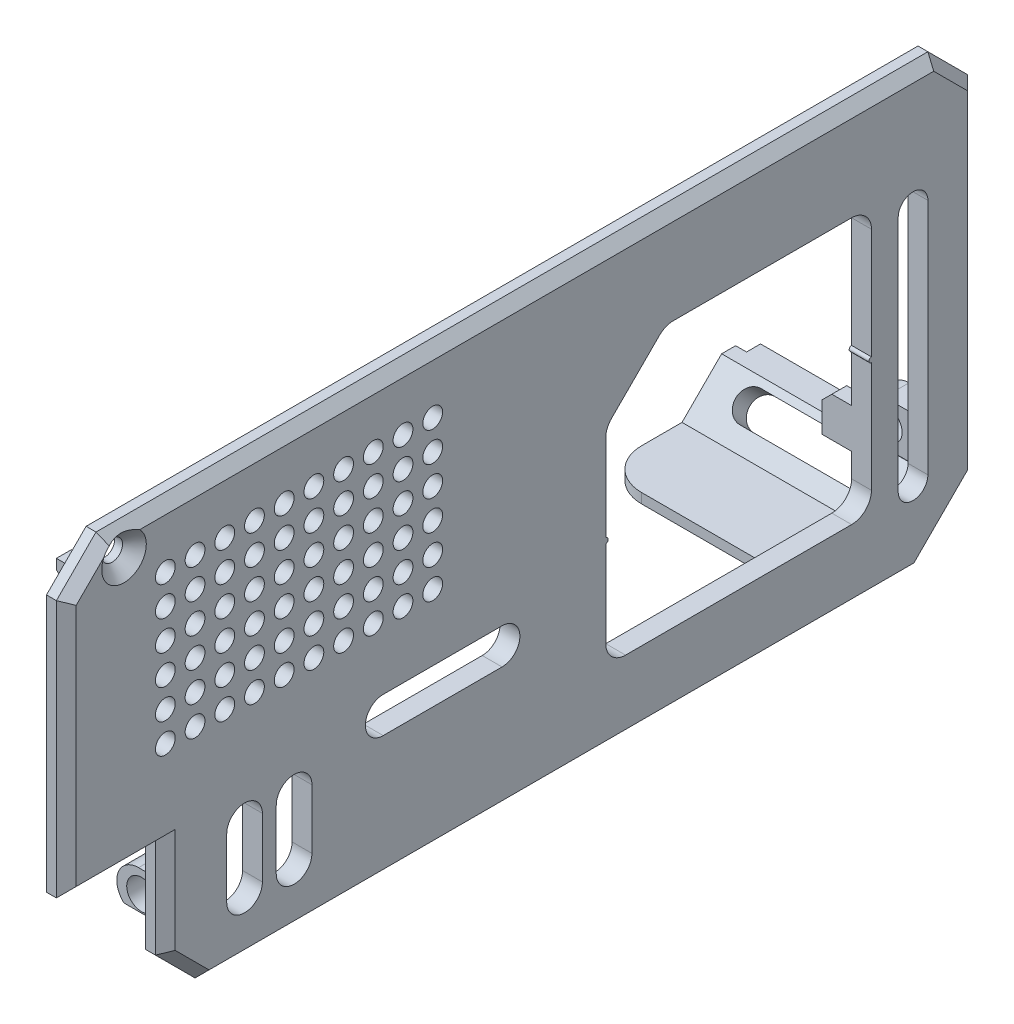
SolidWorks part; units mm, degrees
ref_plane "前视基准面" through (0, 0, 0) normal (0, 0, 1) x (1, 0, 0)
ref_plane "上视基准面" through (0, 0, 0) normal (0, 1, 0) x (1, 0, 0)
ref_plane "右视基准面" through (0, 0, 0) normal (1, 0, 0) x (0, 0, -1)
other "Configuration Table"
sketch "草图1" plane through (0, 0, 0) normal (1, 0, 0) x (0, 0, -1)
  line L0 (61.8678, 29.485) -> (61.8678, -4.515) construction
  line L5 (-16.1322, -10.515) -> (-15.718, -9.515) construction
  line L6 (-20.1322, -6.515) -> (-16.1322, -10.515) construction
  line L14 (61.8678, 29.485) -> (57.8678, 33.485)
  line L15 (61.8678, 29.485) -> (61.8678, -4.515)
  line L16 (55.8678, -10.515) -> (61.8678, -4.515)
  line L17 (-16.1322, -10.515) -> (55.8678, -10.515)
  line L18 (-20.1322, -6.515) -> (-16.1322, -10.515)
  line L19 (-20.1322, 3.485) -> (-20.1322, -6.515)
  line L20 (-30.1322, 3.485) -> (-20.1322, 3.485)
  line L21 (-30.1322, 29.485) -> (-30.1322, 3.485)
  line L22 (-26.1322, 33.485) -> (57.8678, 33.485)
  line L23 (-26.1322, 33.485) -> (-30.1322, 29.485)
extrude "凸台-拉伸1" add sketch "草图1" along normal blind 2
chamfer "倒角1" distance 1 angle 45 10 edges at (2, 31.485, -59.8678) (2, 12.485, -61.8678) (2, -7.515, -58.8678) (2, -10.515, -19.8678) (2, -8.515, 18.1322) (2, -1.515, 20.1322) (2, 3.485, 25.1322) (2, 16.485, 30.1322) (2, 31.485, 28.1322) (2, 33.485, -15.8678)
sketch "草图2" plane through (0, 0, 0) normal (-1, 0, 0) x (0, 0, 1)
  line L10 (-58.7678, 28.2009) -> (-58.7678, -3.231)
  line L11 (-58.7678, -3.231) -> (-54.5838, -7.415)
  line L12 (-54.5838, -7.415) -> (14.8481, -7.415)
  line L13 (14.8481, -7.415) -> (17.0322, -5.231)
  line L14 (17.0322, -5.231) -> (17.0322, 6.585)
  line L15 (17.0322, 6.585) -> (27.0322, 6.585)
  line L16 (27.0322, 6.585) -> (27.0322, 28.2009)
  line L17 (27.0322, 28.2009) -> (24.8481, 30.385)
  line L18 (24.8481, 30.385) -> (-56.5838, 30.385)
  line L19 (-56.5838, 30.385) -> (-58.7678, 28.2009)
  line L20 (-59.7678, 28.6151) -> (-59.7678, -3.6452)
  line L21 (-59.7678, -3.6452) -> (-54.998, -8.415)
  line L22 (-54.998, -8.415) -> (15.2623, -8.415)
  line L23 (15.2623, -8.415) -> (18.0322, -5.6452)
  line L24 (18.0322, -5.6452) -> (18.0322, 5.585)
  line L25 (18.0322, 5.585) -> (28.0322, 5.585)
  line L26 (28.0322, 5.585) -> (28.0322, 28.6151)
  line L27 (28.0322, 28.6151) -> (25.2623, 31.385)
  line L28 (25.2623, 31.385) -> (-56.998, 31.385)
  line L29 (-56.998, 31.385) -> (-59.7678, 28.6151)
  line L30 (-59.7678, 28.6151) -> (-59.7678, -3.6452)
  line L31 (-59.7678, -3.6452) -> (-54.998, -8.415)
  line L32 (-54.998, -8.415) -> (15.2623, -8.415)
  line L33 (15.2623, -8.415) -> (18.0322, -5.6452)
  line L34 (18.0322, -5.6452) -> (18.0322, 5.585)
  line L35 (18.0322, 5.585) -> (28.0322, 5.585)
  line L36 (28.0322, 5.585) -> (28.0322, 28.6151)
  line L37 (28.0322, 28.6151) -> (25.2623, 31.385)
  line L38 (25.2623, 31.385) -> (-56.998, 31.385)
  line L39 (-56.998, 31.385) -> (-59.7678, 28.6151)
  dimension "D1" = 2.1
  dimension "D2" = 1
extrude "凸台-拉伸2" add sketch "草图2" along normal blind 1
sketch "草图3" plane through (0, 0, 0) normal (-1, 0, 0) x (0, 0, 1)
  line L0 (16.1322, -10.515) -> (-55.8678, -10.515) construction
  line L1 (-52.6678, 1.385) -> (-51.1678, 1.385)
  line L2 (-52.6678, 1.385) -> (-52.6678, 5.385)
  line L3 (-52.6678, 5.385) -> (-51.1678, 5.385)
  line L4 (-51.1678, 1.385) -> (-51.1678, 5.385)
  line L5 (0.1322, 1.385) -> (1.6322, 1.385)
  line L6 (0.1322, 1.385) -> (0.1322, 5.385)
  line L7 (0.1322, 5.385) -> (1.6322, 5.385)
  line L8 (1.6322, 1.385) -> (1.6322, 5.385)
  line L9 (-61.8678, -4.515) -> (-61.8678, 29.485) construction
  dimension "D1" = 1.5
  dimension "D2" = 15.9
  dimension "D3" = 4
  dimension "D4" = 9.2
  dimension "D5" = 62
extrude "凸台-拉伸3" add sketch "草图3" along normal blind 3
chamfer "倒角2" distance 1 angle 45 2 edges at (-3, 5.385, 0.8822) (-3, 5.385, -51.9178)
sketch "草图4" plane through (-60, 0, 0) normal (-1, 0, 0) x (0, 0, 1)
  line L0 (30.1322, 29.485) -> (30.1322, 3.485) construction
  line L1 (-57.8678, 33.485) -> (26.1322, 33.485) construction
  circle A0 centre (20.1322, 27.485) radius 1
  circle A1 centre (17.1322, 27.485) radius 1
  circle A2 centre (14.1322, 27.485) radius 1
  circle A3 centre (11.1322, 27.485) radius 1
  circle A4 centre (8.1322, 27.485) radius 1
  circle A5 centre (5.1322, 27.485) radius 1
  circle A7 centre (17.1322, 24.485) radius 1
  circle A8 centre (14.1322, 24.485) radius 1
  circle A9 centre (11.1322, 24.485) radius 1
  circle A10 centre (8.1322, 24.485) radius 1
  circle A11 centre (5.1322, 24.485) radius 1
  circle A13 centre (17.1322, 21.485) radius 1
  circle A14 centre (14.1322, 21.485) radius 1
  circle A15 centre (11.1322, 21.485) radius 1
  circle A16 centre (8.1322, 21.485) radius 1
  circle A17 centre (5.1322, 21.485) radius 1
  circle A19 centre (17.1322, 18.485) radius 1
  circle A20 centre (14.1322, 18.485) radius 1
  circle A21 centre (11.1322, 18.485) radius 1
  circle A22 centre (8.1322, 18.485) radius 1
  circle A23 centre (5.1322, 18.485) radius 1
  circle A25 centre (17.1322, 15.485) radius 1
  circle A26 centre (14.1322, 15.485) radius 1
  circle A27 centre (11.1322, 15.485) radius 1
  circle A28 centre (8.1322, 15.485) radius 1
  circle A29 centre (5.1322, 15.485) radius 1
  circle A31 centre (17.1322, 12.485) radius 1
  circle A32 centre (14.1322, 12.485) radius 1
  circle A33 centre (11.1322, 12.485) radius 1
  circle A34 centre (8.1322, 12.485) radius 1
  circle A35 centre (5.1322, 12.485) radius 1
  circle A43 centre (20.1322, 24.485) radius 1
  circle A44 centre (20.1322, 21.485) radius 1
  circle A45 centre (20.1322, 18.485) radius 1
  circle A46 centre (20.1322, 15.485) radius 1
  circle A47 centre (20.1322, 12.485) radius 1
  circle A48 centre (2.1322, 27.485) radius 1
  circle A49 centre (-0.8678, 27.485) radius 1
  circle A50 centre (-3.8678, 27.485) radius 1
  circle A51 centre (-6.8678, 27.485) radius 1
  circle A52 centre (2.1322, 24.485) radius 1
  circle A53 centre (-0.8678, 24.485) radius 1
  circle A54 centre (-3.8678, 24.485) radius 1
  circle A55 centre (-6.8678, 24.485) radius 1
  circle A56 centre (2.1322, 21.485) radius 1
  circle A57 centre (-0.8678, 21.485) radius 1
  circle A58 centre (-3.8678, 21.485) radius 1
  circle A59 centre (-6.8678, 21.485) radius 1
  circle A60 centre (2.1322, 18.485) radius 1
  circle A61 centre (-0.8678, 18.485) radius 1
  circle A62 centre (-3.8678, 18.485) radius 1
  circle A63 centre (-6.8678, 18.485) radius 1
  circle A64 centre (2.1322, 15.485) radius 1
  circle A65 centre (-0.8678, 15.485) radius 1
  circle A66 centre (-3.8678, 15.485) radius 1
  circle A67 centre (-6.8678, 15.485) radius 1
  circle A68 centre (2.1322, 12.485) radius 1
  circle A69 centre (-0.8678, 12.485) radius 1
  circle A70 centre (-3.8678, 12.485) radius 1
  circle A71 centre (-6.8678, 12.485) radius 1
  dimension "D3" = 2
  dimension "D1" = 10
  dimension "D2" = 6
  dimension "D4" = 10
  dimension "D5" = 6
extrude "切除-拉伸1" cut sketch "草图4" against normal up to next
sketch "草图5" plane through (0, 0, 0) normal (-1, 0, 0) x (0, 0, 1)
  line L0 (20.1322, 3.485) -> (20.1322, -6.515) construction
  line L1 (16.1322, -10.515) -> (-55.8678, -10.515) construction
  line L4 (13.9322, -4.515) -> (13.9322, 1.485)
  line L5 (10.3322, 1.485) -> (10.3322, -4.515)
  line L8 (5.3322, 1.485) -> (5.3322, -4.515)
  line L9 (8.9322, -4.515) -> (8.9322, 1.485)
  arc A4 (13.9322, 1.485) -> (10.3322, 1.485) centre (12.1322, 1.485) ccw
  arc A5 (10.3322, -4.515) -> (13.9322, -4.515) centre (12.1322, -4.515) ccw
  arc A8 (8.9322, 1.485) -> (5.3322, 1.485) centre (7.1322, 1.485) ccw
  arc A9 (5.3322, -4.515) -> (8.9322, -4.515) centre (7.1322, -4.515) ccw
  dimension "D1" = 8
  dimension "D2" = 5
  dimension "D3" = 6
extrude "切除-拉伸2" cut sketch "草图5" against normal up to next
sketch "草图6" plane through (0, 0, 0) normal (-1, 0, 0) x (0, 0, 1)
  line L0 (-55.3678, 21.485) -> (-55.3678, -2.515) construction
  line L1 (-53.8678, 21.485) -> (-53.8678, -2.515)
  line L2 (-56.8678, 21.485) -> (-56.8678, -2.515)
  line L3 (-57.8678, 33.485) -> (26.1322, 33.485) construction
  line L4 (16.1322, -10.515) -> (-55.8678, -10.515) construction
  line L5 (-61.8678, -4.515) -> (-61.8678, 29.485) construction
  arc A0 (-53.8678, 21.485) -> (-56.8678, 21.485) centre (-55.3678, 21.485) ccw
  arc A1 (-56.8678, -2.515) -> (-53.8678, -2.515) centre (-55.3678, -2.515) ccw
  point P2 (-55.3678, 9.485)
  dimension "D4" = 1.5
  dimension "D1" = 12
  dimension "D2" = 8
  dimension "D3" = 6.5
extrude "切除-拉伸3" cut sketch "草图6" against normal up to next
sketch "草图7" plane through (0, 0, 0) normal (-1, 0, 0) x (0, 0, 1)
  line L1 (22.6322, 27.185) -> (24.1322, 27.185)
  line L2 (22.6322, 27.185) -> (22.6322, 25.185)
  line L3 (22.6322, 25.185) -> (24.1322, 25.185)
  line L4 (24.1322, 27.185) -> (24.1322, 25.185)
  line L8 (22.6322, 23.235) -> (22.6322, 27.235) construction
  line L9 (29.3879, 25.185) -> (12.7179, 25.185) construction
  dimension "D1" = 1.5
  dimension "D2" = 2
extrude "凸台-拉伸4" add sketch "草图7" along normal blind 5
chamfer "倒角3" distance 1 angle 45 1 edges at (-5, 25.185, 23.3822)
sketch "草图9" plane through (0, 0, 0) normal (-1, 0, 0) x (0, 0, 1)
  line L0 (16.1322, -10.515) -> (-55.8678, -10.515) construction
  line L2 (-51.1678, 21.8134) -> (-51.1678, -1.015)
  line L5 (-49.1678, -3.015) -> (-26.3394, -3.015)
  line L7 (-61.8678, 29.485) -> (-61.8678, -4.515) construction
  line L9 (-24.3394, -1.015) -> (-24.3394, 16.985)
  line L10 (-49.1678, 23.8134) -> (-31.1678, 23.8134)
  line L11 (-29.7536, 23.2276) -> (-24.9252, 18.3992)
  line L12 (-55.8678, -10.515) -> (16.1322, -10.515) construction
  arc A2 (-51.1678, -1.015) -> (-49.1678, -3.015) centre (-49.1678, -1.015) ccw
  arc A3 (-49.1678, 23.8134) -> (-51.1678, 21.8134) centre (-49.1678, 21.8134) ccw
  arc A4 (-26.3394, -3.015) -> (-24.3394, -1.015) centre (-26.3394, -1.015) ccw
  arc A5 (-24.3394, 16.985) -> (-24.9252, 18.3992) centre (-26.3394, 16.985) ccw
  arc A6 (-31.1678, 23.8134) -> (-29.7536, 23.2276) centre (-31.1678, 21.8134) cw
  point P15 (-51.1678, -4.015)
  point P18 (-51.1678, 19.985)
  point P22 (-30.3394, 23.8134)
  dimension "D3" = 6
  dimension "D5" = 20
  dimension "D6" = 10.7
  dimension "D4" = 2
  dimension "D1" = 24
  dimension "D2" = 6.5
  dimension "D7" = 20
  dimension "D8" = 7.5
extrude "切除-拉伸6" cut sketch "草图9" against normal up to next
sketch "草图8" plane through (0, 0, 0) normal (-1, 0, 0) x (0, 0, 1)
  line L0 (-50.7499, 10.685) -> (-0.2499, 10.685) construction
  line L5 (3.1322, 10.685) -> (1.1322, 10.685)
  line L6 (3.1322, 10.685) -> (3.1322, 5.685)
  line L7 (3.1322, 5.685) -> (1.1322, 5.685)
  line L8 (1.1322, 10.685) -> (1.1322, 5.685)
  line L11 (-61.8678, -4.515) -> (-61.8678, 29.485) construction
  dimension "D1" = 65
  dimension "D2" = 2
  dimension "D3" = 5
extrude "凸台-拉伸5" add sketch "草图8" along normal blind 1
sketch "草图12" plane through (0, 0, 0) normal (-1, 0, 0) x (0, 0, 1)
  line L0 (-59.7678, 28.6151) -> (-59.7678, -3.6452) construction
  line L1 (-59.7678, 26.485) -> (-57.2678, 26.485)
  line L2 (-59.7678, 26.485) -> (-59.7678, 22.085)
  line L3 (-59.7678, 22.085) -> (-57.2678, 22.085)
  line L4 (-57.2678, 26.485) -> (-57.2678, 22.085)
  line L5 (-57.8678, 33.485) -> (26.1322, 33.485) construction
  line L6 (16.1322, -10.515) -> (-55.8678, -10.515) construction
  line L7 (-59.7678, -2.715) -> (-57.2678, -2.715)
  line L8 (-59.7678, -2.715) -> (-59.7678, 1.685)
  line L9 (-59.7678, 1.685) -> (-57.2678, 1.685)
  line L10 (-57.2678, -2.715) -> (-57.2678, 1.685)
  dimension "D1" = 2.5
  dimension "D2" = 7
  dimension "D3" = 4.4
  dimension "D4" = 7.8
extrude "凸台-拉伸6" add sketch "草图12" along normal blind 5
sketch "草图14" plane through (0, 0, -59.7678) normal (0, 0, -1) x (-1, 0, 0)
  circle A0 centre (2.5, 24.285) radius 1.5
  circle A1 centre (2.5, -0.515) radius 1.5
  dimension "D1" = 3
extrude "切除-拉伸7" cut sketch "草图14" against normal up to next
sketch "草图16" plane through (0, 0, 0) normal (-1, 0, 0) x (0, 0, 1)
  line L5 (15.5322, -6.215) -> (17.4623, -6.215)
  line L6 (17.4623, -6.215) -> (18.0322, -5.6452)
  line L7 (18.0322, -5.6452) -> (18.0322, -1.815)
  line L8 (18.0322, -1.815) -> (15.5322, -1.815)
  line L9 (15.5322, -1.815) -> (15.5322, -6.215)
  line L10 (15.5322, -6.215) -> (17.4623, -6.215)
  line L11 (17.4623, -6.215) -> (18.0322, -5.6452)
  line L12 (18.0322, -5.6452) -> (18.0322, -1.815)
  line L13 (18.0322, -1.815) -> (15.5322, -1.815)
  line L14 (15.5322, -1.815) -> (15.5322, -6.215)
  dimension "D1" = 0
extrude "凸台-拉伸7" add sketch "草图16" along normal blind 5
sketch "草图17" plane through (0, 0, 18.0322) normal (0, 0, 1) x (1, 0, 0)
  circle A0 centre (-2.5, -4.015) radius 1.5
  dimension "D1" = 3
extrude "切除-拉伸8" cut sketch "草图17" against normal up to next
fillet "圆角1" radius 2.2 6 edges at (-5, 22.085, -58.5178) (-5, 26.485, -58.5178) (-5, 1.685, -58.5178) (-5, -2.715, -58.5178) (-5, -6.215, 16.4973) (-5, -1.815, 16.7822)
sketch "草图18" plane through (-1, 0, 0) normal (-1, 0, 0) x (0, 0, 1)
  line L1 (24.0322, 32.485) -> (29.1322, 32.485)
  line L2 (24.0322, 32.485) -> (24.0322, 28.785)
  line L3 (24.0322, 28.785) -> (29.1322, 28.785)
  line L4 (29.1322, 32.485) -> (29.1322, 28.785)
  line L5 (29.1322, 29.0707) -> (29.1322, 4.485) construction
  line L6 (-57.4536, 32.485) -> (25.718, 32.485) construction
  line L7 (30.1322, 29.485) -> (30.1322, 3.485) construction
  line L8 (-57.8678, 33.485) -> (26.1322, 33.485) construction
  dimension "D1" = 6.1
  dimension "D2" = 4.7
extrude "切除-拉伸9" cut sketch "草图18" against normal blind 1
sketch "草图19" plane through (2, 0, 0) normal (1, 0, 0) x (0, 0, -1)
  circle A0 centre (-24.3038, 30.885) radius 1.05
  dimension "D1" = 2.1
extrude "切除-拉伸10" cut sketch "草图19" against normal up to next
chamfer "倒角4" distance 1.2 angle 45 1 edges at (2, 30.885, 23.2538)
sketch "草图20" plane through (0, 0, 0) normal (-1, 0, 0) x (0, 0, 1)
  line L6 (-60.595, -4.515) -> (-55.495, -9.615)
  line L7 (-59.0394, -4.515) -> (-60.595, -4.515)
  line L8 (-55.0394, -8.515) -> (-59.0394, -4.515)
  line L9 (-50.8678, -8.515) -> (-55.0394, -8.515)
  line L10 (-50.8678, -9.615) -> (-50.8678, -8.515)
  line L11 (-61.8678, -4.515) -> (-55.8678, -10.515)
  line L13 (-59.0394, -4.515) -> (-61.8678, -4.515)
  line L14 (-55.0394, -8.515) -> (-59.0394, -4.515)
  line L15 (-46.8678, -8.515) -> (-55.0394, -8.515)
  line L30 (-55.495, -9.615) -> (-50.8678, -9.615)
  line L31 (-55.8678, -10.515) -> (-46.8678, -10.515)
  line L32 (16.1322, -10.515) -> (-55.8678, -10.515) construction
  line L51 (-46.8678, -10.515) -> (-46.8678, -8.515)
  dimension "D1" = 0
extrude "凸台-拉伸8" add sketch "草图20" along normal blind 21
sketch "草图21" plane through (-21, 0, 0) normal (-1, 0, 0) x (0, 0, 1)
  line L0 (-60.595, -4.515) -> (-59.0394, -4.515) construction
  line L6 (-55.4536, -9.515) -> (-46.8678, -9.515)
  line L7 (-60.4536, -4.515) -> (-55.4536, -9.515)
  line L17 (-60.4536, -4.515) -> (-61.8678, -4.515)
  line L18 (-61.8678, -4.515) -> (-55.8678, -10.515)
  line L19 (-55.8678, -10.515) -> (-46.8678, -10.515)
  line L20 (-46.8678, -10.515) -> (-46.8678, -9.515)
extrude "切除-拉伸13" cut sketch "草图21" against normal blind 1.1
sketch "草图23" plane through (0, 0, -46.8678) normal (0, 0, 1) x (1, 0, 0)
  line L1 (-19.9, -9.515) -> (0, -9.515)
  line L2 (-19.9, -9.515) -> (-19.9, -10.515)
  line L3 (-19.9, -10.515) -> (0, -10.515)
  line L4 (0, -9.515) -> (0, -10.515)
extrude "切除-拉伸14" cut sketch "草图23" against normal blind 1.1
fillet "圆角2" radius 3.1 1 edges at (-19.9, -10.015, -47.9678)
fillet "圆角3" radius 4.1 1 edges at (-21, -9.015, -46.8678)
sketch "草图24" plane through (0, -33.1914, -33.1914) normal (0, -0.7071, -0.7071) x (1, 0, 0)
  line L0 (-4.5, -36.3119) -> (-16.5, -36.3119) construction
  line L1 (-4.5, -37.8119) -> (-16.5, -37.8119)
  line L2 (-4.5, -34.8119) -> (-16.5, -34.8119)
  line L4 (-19.9, -40.5545) -> (-19.9, -32.0693) construction
  line L5 (-21, -32.4835) -> (-21, -39.5545) construction
  arc A0 (-4.5, -37.8119) -> (-4.5, -34.8119) centre (-4.5, -36.3119) ccw
  arc A1 (-16.5, -34.8119) -> (-16.5, -37.8119) centre (-16.5, -36.3119) ccw
  point P2 (-10.5, -36.3119)
  point P10 (-19.9, -36.3119)
  dimension "D1" = 1.5
  dimension "D2" = 12
  dimension "D3" = 4.5
extrude "切除-拉伸15" cut sketch "草图24" against normal through all
sketch "草图28" plane through (-1, 0, 0) normal (-1, 0, 0) x (0, 0, 1)
  line L0 (30.1322, 29.485) -> (30.1322, 3.485) construction
  line L8 (28.0556, 31.485) -> (22.0556, 31.485)
  line L9 (28.0556, 28.7839) -> (28.0556, 31.485)
  line L10 (22.0556, 28.7839) -> (28.0556, 28.7839)
  line L11 (22.0556, 31.485) -> (22.0556, 28.7839)
  dimension "D1" = 2.0766
  dimension "D2" = 6
extrude "切除-拉伸17" cut sketch "草图28" against normal up to surface (1 mm away) up to face at (0, 26.185, 23.3822)
sketch "草图29" plane through (2, 0, 0) normal (1, 0, 0) x (0, 0, -1)
  line L0 (13.8678, 3.985) -> (1.8678, 3.985) construction
  line L1 (13.8678, 2.185) -> (1.8678, 2.185)
  line L2 (13.8678, 5.785) -> (1.8678, 5.785)
  line L3 (-20.1322, -6.515) -> (-20.1322, 3.485) construction
  line L4 (55.8678, -10.515) -> (-16.1322, -10.515) construction
  arc A0 (13.8678, 2.185) -> (13.8678, 5.785) centre (13.8678, 3.985) ccw
  arc A1 (1.8678, 5.785) -> (1.8678, 2.185) centre (1.8678, 3.985) ccw
  point P2 (7.8678, 3.985)
  dimension "D4" = 1.8
  dimension "D1" = 22
  dimension "D2" = 12
  dimension "D3" = 14.5
extrude "切除-拉伸18" cut sketch "草图29" against normal up to next
sketch "草图30" plane through (2, 0, 0) normal (1, 0, 0) x (0, 0, -1)
  line L0 (24.3394, -1.015) -> (24.3394, 16.985) construction
  line L1 (51.1678, 21.8134) -> (51.1678, -1.015) construction
  circle A0 centre (24.3394, 7.985) radius 0.25
  circle A1 centre (51.1678, 10.3992) radius 0.25
  dimension "D1" = 0.5
extrude "凸台-拉伸9" add sketch "草图30" against normal blind 2
